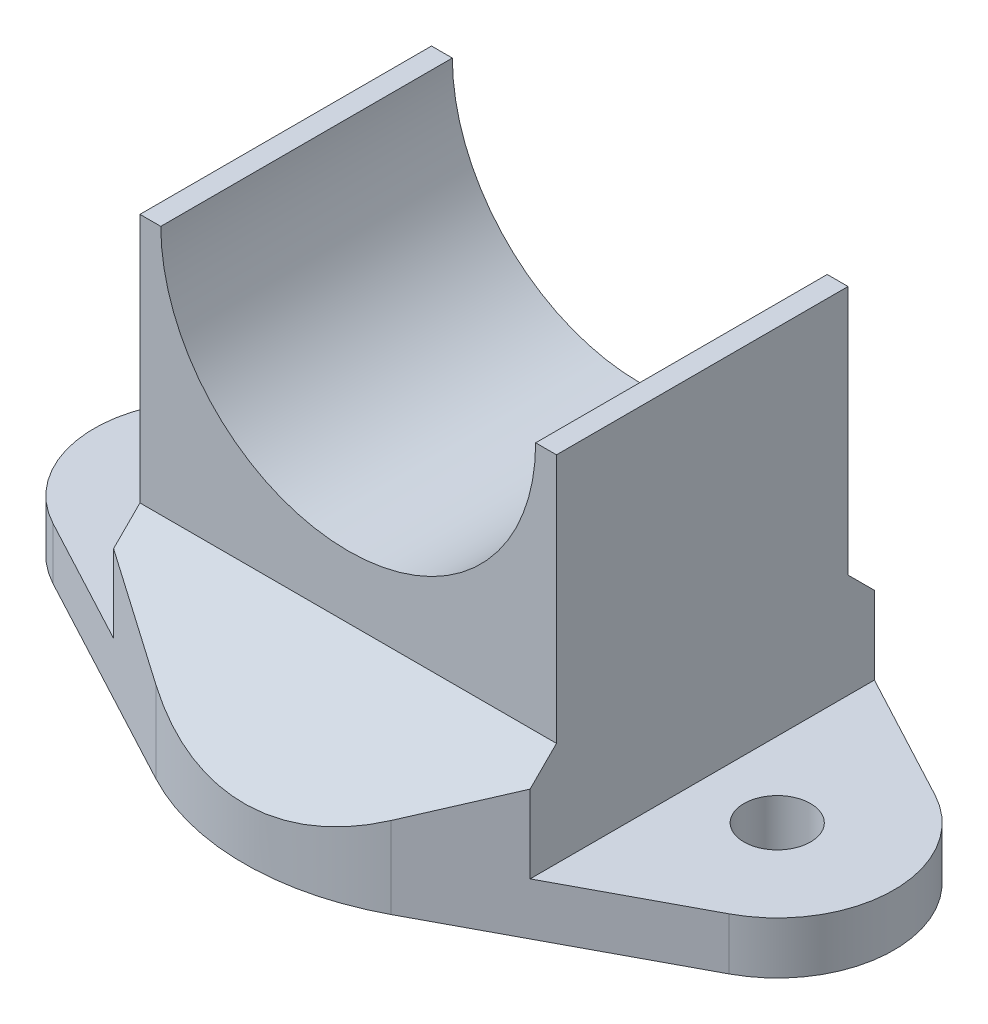
SolidWorks part; units mm, degrees
ref_plane "前视基准面" through (0, 0, 0) normal (0, 0, 1) x (1, 0, 0)
ref_plane "上视基准面" through (0, 0, 0) normal (0, 1, 0) x (1, 0, 0)
ref_plane "右视基准面" through (0, 0, 0) normal (1, 0, 0) x (0, 0, -1)
sketch "草图1" plane through (0, 0, 0) normal (0, 1, 0) x (1, 0, 0)
  line L1 (16.2353, -4.9412) -> (5.6471, -10.5882)
  line L2 (-16.2353, 4.9412) -> (-5.6471, 10.5882)
  line L3 (-16.2353, -4.9412) -> (-5.6471, -10.5882)
  line L4 (16.2353, 4.9412) -> (5.6471, 10.5882)
  circle A0 centre (-13.6, 0) radius 1.6
  circle A1 centre (13.6, 0) radius 1.6
  arc A2 (-16.2353, 4.9412) -> (-16.2353, -4.9412) centre (-13.6, 0) ccw
  arc A3 (16.2353, -4.9412) -> (16.2353, 4.9412) centre (13.6, 0) ccw
  arc A4 (-5.6471, -10.5882) -> (5.6471, -10.5882) centre (0, 0) ccw
  arc A5 (5.6471, 10.5882) -> (-5.6471, 10.5882) centre (0, 0) ccw
extrude "凸台-拉伸1" add sketch "草图1" against normal blind 2.5
sketch "草图2" plane through (0, 0, 0) normal (1, 0, 0) x (0, 0, -1)
  line L0 (12, 0) -> (-12, 0)
  line L1 (-10.5882, 0) -> (-12, 0) construction
  line L2 (-7, 5) -> (-7, 17)
  line L4 (-7, 5) -> (-12, 0)
  line L6 (7, 5) -> (12, 0)
  line L7 (7, 5) -> (7, 17)
  line L8 (-7, 17) -> (7, 17)
extrude "凸台-拉伸2" add sketch "草图2" along normal blind 10 and the other way blind 10
sketch "草图4" plane through (0, 0, 0) normal (0, 1, 0) x (1, 0, 0)
  line L0 (5.6471, -10.5882) -> (10, -8.2667) construction
  line L1 (-10, -8.2667) -> (-5.6471, -10.5882) construction
  line L2 (-5.6471, 10.5882) -> (-10, 8.2667) construction
  line L3 (10, 8.2667) -> (5.6471, 10.5882) construction
  line L4 (10, -8.2667) -> (16.2353, -4.9412) construction
  line L5 (16.2353, 4.9412) -> (10, 8.2667) construction
  line L6 (-10, 8.2667) -> (-16.2353, 4.9412) construction
  line L7 (-16.2353, -4.9412) -> (-10, -8.2667) construction
  line L8 (5.6471, -10.5882) -> (10, -8.2667)
  line L9 (-10, -8.2667) -> (-5.6471, -10.5882)
  line L10 (-5.6471, 10.5882) -> (-10, 8.2667)
  line L11 (10, 8.2667) -> (5.6471, 10.5882)
  line L12 (10, -8.2667) -> (16.2353, -4.9412)
  line L13 (16.2353, 4.9412) -> (10, 8.2667)
  line L14 (-10, 8.2667) -> (-16.2353, 4.9412)
  line L15 (-16.2353, -4.9412) -> (-10, -8.2667)
  arc A0 (0, -12) -> (5.6471, -10.5882) centre (0, 0) ccw construction
  arc A1 (-5.6471, -10.5882) -> (0, -12) centre (0, 0) ccw construction
  arc A2 (0, 12) -> (-5.6471, 10.5882) centre (0, 0) ccw construction
  arc A3 (5.6471, 10.5882) -> (0, 12) centre (0, 0) ccw construction
  arc A4 (16.2353, -4.9412) -> (16.2353, 4.9412) centre (13.6, 0) ccw construction
  arc A5 (-16.2353, 4.9412) -> (-16.2353, -4.9412) centre (-13.6, 0) ccw construction
  arc A6 (0, -12) -> (5.6471, -10.5882) centre (0, 0) ccw
  arc A7 (-5.6471, -10.5882) -> (0, -12) centre (0, 0) ccw
  arc A8 (0, 12) -> (-5.6471, 10.5882) centre (0, 0) ccw
  arc A9 (5.6471, 10.5882) -> (0, 12) centre (0, 0) ccw
  arc A10 (16.2353, -4.9412) -> (16.2353, 4.9412) centre (13.6, 0) ccw
  arc A11 (-16.2353, 4.9412) -> (-16.2353, -4.9412) centre (-13.6, 0) ccw
  circle A12 centre (0, 0) radius 25
extrude "切除-拉伸3" cut sketch "草图4" along normal blind 12
sketch "草图5" plane through (0, 0, 0) normal (0, 0, 1) x (1, 0, 0)
  line L0 (-10, 17) -> (10, 17) construction
  circle A0 centre (0, 17) radius 9
extrude "切除-拉伸4" cut sketch "草图5" against normal blind 12 and the other way blind 12
